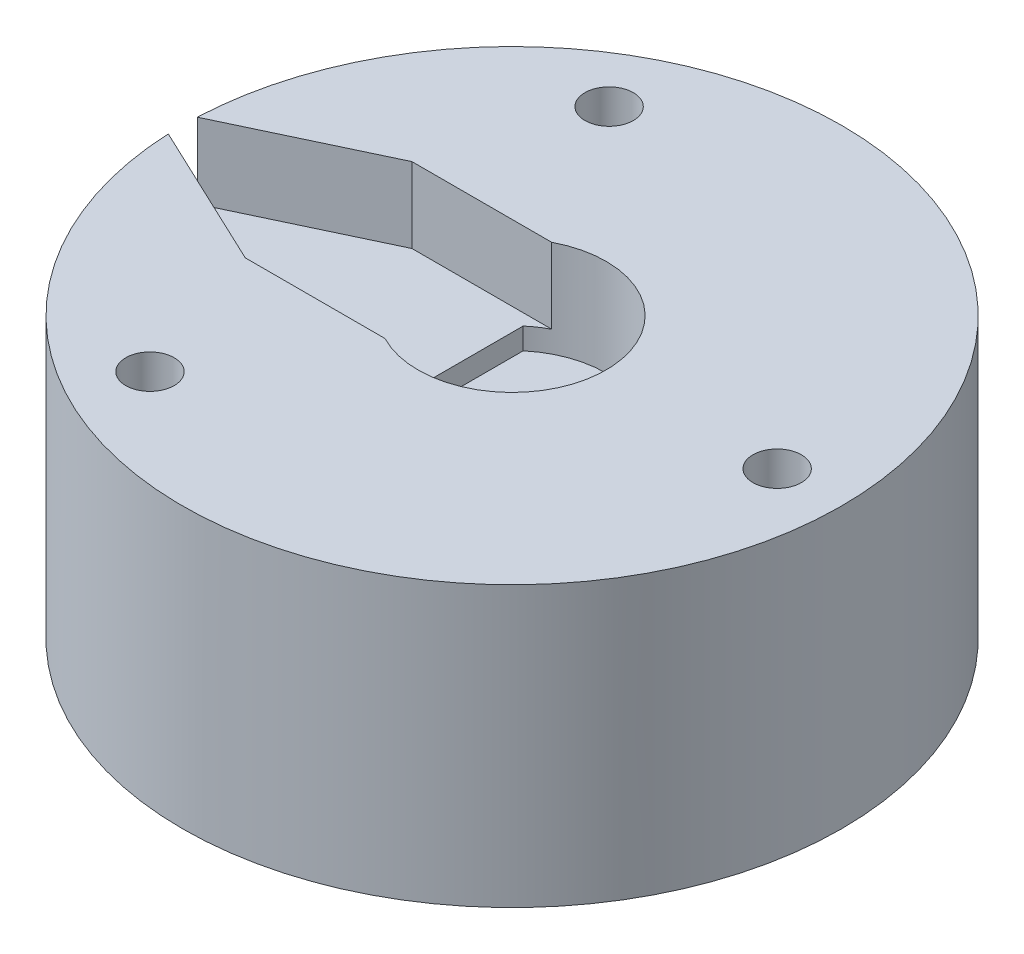
SolidWorks part; units mm, degrees
ref_plane "Спереди" through (0, 0, 0) normal (0, 0, 1) x (1, 0, 0)
ref_plane "Сверху" through (0, 0, 0) normal (0, 1, 0) x (1, 0, 0)
ref_plane "Справа" through (0, 0, 0) normal (1, 0, 0) x (0, 0, -1)
sketch "Эскиз1" plane through (0, 0, 0) normal (0, 0, 1) x (1, 0, 0)
  line L0 (0, 0) -> (0, 47.8003) construction
  line L1 (0, 26) -> (30.65, 26)
  line L2 (30.65, 26) -> (30.65, 0)
  line L3 (30.65, 0) -> (18.65, 0)
  line L4 (18.65, 0) -> (18.65, 7)
  line L5 (18.65, 7) -> (17.15, 7)
  line L6 (17.15, 7) -> (17.15, 13.5)
  line L7 (17.15, 13.5) -> (3.65, 13.5)
  line L8 (3.65, 13.5) -> (3.65, 17)
  line L9 (3.65, 17) -> (0, 17)
  line L10 (0, 17) -> (0, 26)
  dimension "D1" = 18.65
  dimension "D2" = 1.5
  dimension "D3" = 7
  dimension "D4" = 9
  dimension "D5" = 6.5
  dimension "D6" = 26
  dimension "D7" = 3.65
  dimension "D8" = 12
revolve "Повернуть1" add sketch "Эскиз1" angle 360 about L0
sketch "Эскиз под резистор" plane through (0, 26, 0) normal (0, 1, 0) x (1, 0, 0)
  line L3 (5.65, 6.6813) -> (5.65, -6.6813)
  line L4 (-5.65, 6.6813) -> (-5.65, -6.6813)
  line L5 (-17.062, 7.75) -> (-30.6203, 1.35)
  line L6 (-17.062, 7.75) -> (-4.062, 7.75)
  line L8 (-17.062, -7.75) -> (-4.062, -7.75)
  line L9 (-4.062, 7.75) -> (-4.062, -7.75)
  line L10 (-17.062, -7.75) -> (-30.6203, -1.35)
  arc A0 (-5.65, -6.6813) -> (5.65, -6.6813) centre (0, 0) ccw
  arc A5 (-5.65, -6.6813) -> (5.65, -6.6813) centre (0, 0) ccw
  arc A7 (5.65, 6.6813) -> (-5.65, 6.6813) centre (0, 0) ccw
  circle A8 centre (0, 0) radius 8.75
  circle A9 centre (0, 0) radius 30.65 construction
  arc A10 (-30.6203, -1.35) -> (-30.6203, 1.35) centre (0, 0) cw
  point P7 (-4.062, 0)
  point P9 (-30.65, 0)
  point P14 (5.65, 0)
  point P20 (0, 8.75)
  dimension "D1" = 8.75
  dimension "D2" = 11.3
  dimension "D3" = 17.5
  dimension "D6" = 2.7
  dimension "D4" = 15.5
  dimension "D5" = 13
extrude "Выемка под резистор" cut sketch "Эскиз под резистор" against normal blind 9 contours L3 A7 L9 A0 | L9 A7 L4 A0 region at (0.6971, 26, 0) region at (-4.8366, 26, 0)
sketch "Эскиз выемки" plane through (0, 17, 0) normal (0, 1, 0) x (1, 0, 0)
  line L0 (-0.92, -7.2) -> (0.92, -7.2)
  line L1 (1.5, -7.78) -> (1.5, -8.0822)
  line L2 (-1.5, -7.78) -> (-1.5, -8.0822)
  arc A0 (-0.9471, -8.6986) -> (0.9471, -8.6986) centre (0, 0) ccw
  arc A1 (0.9471, -8.6986) -> (1.5, -8.0822) centre (0.88, -8.0822) ccw
  arc A2 (-0.9471, -8.6986) -> (-1.5, -8.0822) centre (-0.88, -8.0822) cw
  arc A3 (1.5, -7.78) -> (0.92, -7.2) centre (0.92, -7.78) ccw
  arc A4 (-1.5, -7.78) -> (-0.92, -7.2) centre (-0.92, -7.78) cw
  arc A5 (-5.65, -6.6813) -> (5.65, -6.6813) centre (0, 0) ccw construction
  point P6 (0, -7.2)
  dimension "D1" = 0.58
  dimension "D2" = 0.62
  dimension "D3" = 3
  dimension "D4" = 7.2
extrude "Вырез выемки" cut sketch "Эскиз выемки" against normal blind 2
extrude "Вырез под резистор" cut sketch "Эскиз под резистор<3>" against normal blind 7 contours A8 A7 L6 L8 A0 | L3 A8 | L4 A8 region at (6.911, 26, 0) region at (-16.7148, 26, 0) region at (-6.911, 26, 0)
sketch "Эскиз под резистор<3>" plane through (0, 26, 0) normal (0, 1, 0) x (1, 0, 0) same geometry as "Эскиз под резистор"
sketch "Под винты" plane through (0, 26, 0) normal (0, 1, 0) x (1, 0, 0)
  line L1 (0, 0) -> (24.65, 0) construction
  circle A0 centre (0, 0) radius 24.65
  circle A1 centre (24.65, 0) radius 2.25
  circle A2 centre (24.65, 0) radius 3.55
  circle A7 centre (-12.325, -21.3475) radius 3.55
  circle A8 centre (-12.325, -21.3475) radius 2.25
  circle A9 centre (-12.325, 21.3475) radius 3.55
  circle A10 centre (-12.325, 21.3475) radius 2.25
  dimension "D1" = 49.3
  dimension "D2" = 7.1
  dimension "D3" = 4.5
  dimension "D5" = 24.65
  dimension "D4" = 3
extrude "Отверстия" cut sketch "Под винты" against normal through all contours A10 | A1 | A8
